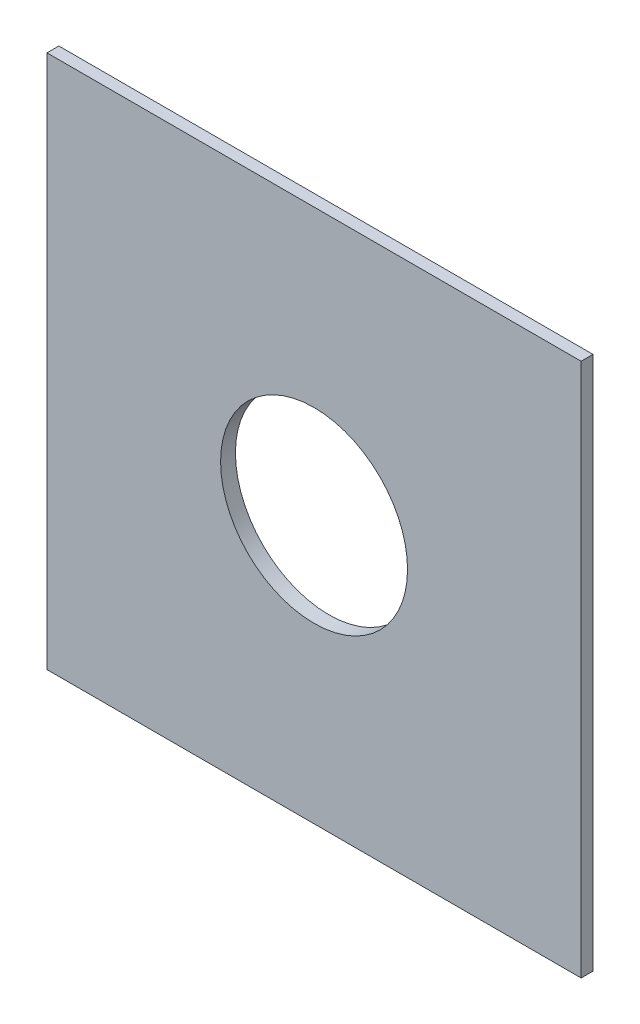
SolidWorks part; units mm, degrees
ref_plane "Front Plane" through (0, 0, 0) normal (0, 0, 1) x (1, 0, 0)
ref_plane "Top Plane" through (0, 0, 0) normal (0, 1, 0) x (1, 0, 0)
ref_plane "Right Plane" through (0, 0, 0) normal (1, 0, 0) x (0, 0, -1)
sketch "Sketch1" plane through (0, 0, 0) normal (0, 0, 1) x (1, 0, 0)
  line L1 (-90, -90) -> (90, -90)
  line L2 (-90, -90) -> (-90, 90)
  line L3 (-90, 90) -> (90, 90)
  line L4 (90, -90) -> (90, 90)
  line L5 (-90, -90) -> (90, 90) construction
  line L6 (-90, 90) -> (90, -90) construction
  circle A0 centre (0, 0) radius 31.5
  point P7 (88.4858, 37.0822)
  point P8 (87.1561, 87.1561)
  dimension "D1" = 63
  dimension "D2" = 180
extrude "Boss-Extrude1" add sketch "Sketch1" against normal blind 4
sketch "Diagram" plane through (0, 0, -4) normal (0, 0, -1) x (-1, 0, 0)
  line L0 (-283.6654, -38.7824) -> (417.6679, -38.7824) construction
  line L1 (-289.1527, 18.7774) -> (-47.1527, 18.7774) construction
sketch "Sketch6" plane through (0, 0, -4) normal (0, 0, -1) x (-1, 0, 0)
  line L0 (-52, -21.5391) -> (-21.5391, -52)
  line L1 (22.7817, 55) -> (-22.7817, 55)
  line L2 (-22.7817, 55) -> (-55, 22.7817)
  line L3 (-55, 22.7817) -> (-55, -22.7817)
  line L4 (-55, -22.7817) -> (-22.7817, -55)
  line L5 (-22.7817, -55) -> (22.7817, -55)
  line L6 (22.7817, -55) -> (55, -22.7817)
  line L7 (55, -22.7817) -> (55, 22.7817)
  line L8 (55, 22.7817) -> (22.7817, 55)
  line L9 (-21.5391, -52) -> (21.5391, -52)
  line L10 (21.5391, -52) -> (52, -21.5391)
  line L11 (52, -21.5391) -> (52, 21.5391)
  line L12 (52, 21.5391) -> (21.5391, 52)
  line L13 (21.5391, 52) -> (-21.5391, 52)
  line L14 (-21.5391, 52) -> (-52, 21.5391)
  line L15 (-52, 21.5391) -> (-52, -21.5391)
  circle A1 centre (0, 0) radius 55 construction
  circle A2 centre (0, 0) radius 38.5
  circle M4 centre (0, 0) radius 31.5
  dimension "D3" = 77
  dimension "D1" = 110
  dimension "D2" = 3
extrude "Boss-Extrude2" add sketch "Sketch6" along normal blind 2 contours L7 L8 L1 L2 L3 L4 L5 L6 L15 L14 L13 L12 L11 L10 L9 L0 region at (-37.7909, 37.7909, -4)
extrude "Boss-Extrude3" add sketch "Sketch6<3>" along normal blind 1 contours A2 M4 region at (37.4111, 0, -4)
sketch "Sketch6<3>" plane through (0, 0, -4) normal (0, 0, -1) x (-1, 0, 0) same geometry as "Sketch6"
